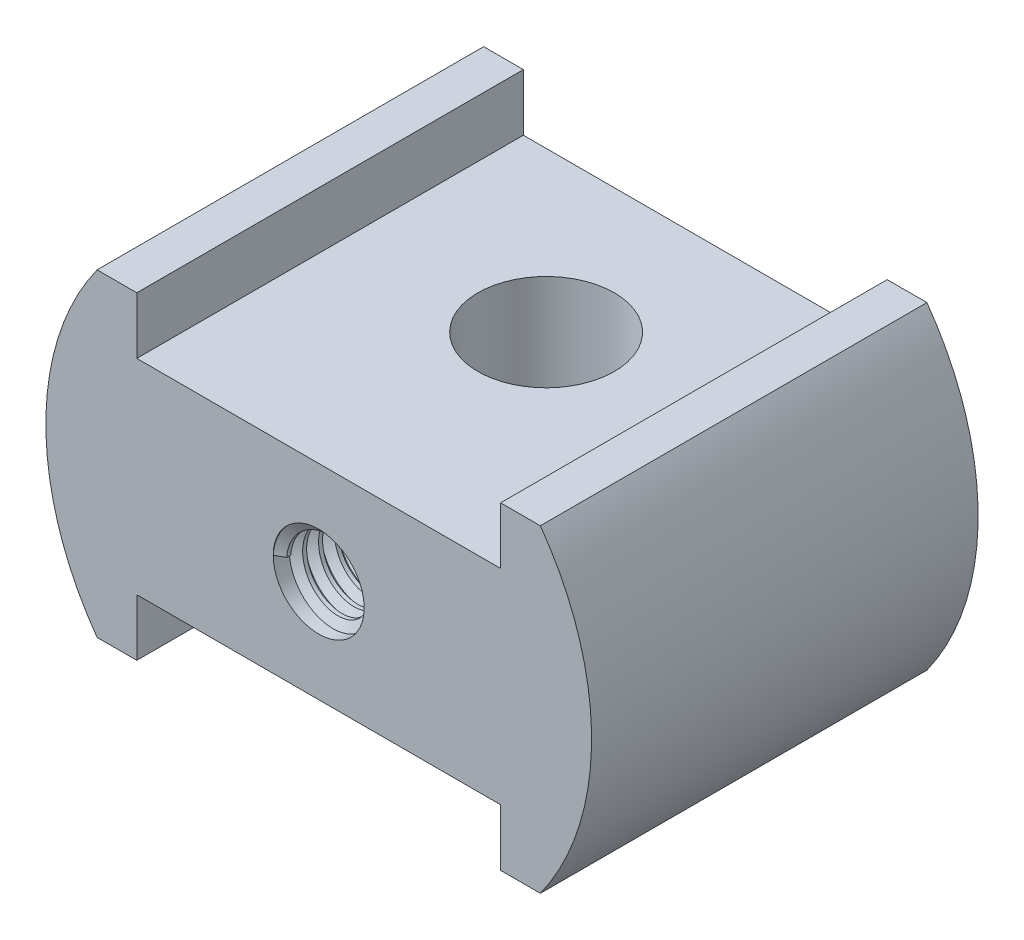
SolidWorks part; units mm, degrees
ref_plane "Front Plane" through (0, 0, 0) normal (0, 0, 1) x (1, 0, 0)
ref_plane "Top Plane" through (0, 0, 0) normal (0, 1, 0) x (1, 0, 0)
ref_plane "Right Plane" through (0, 0, 0) normal (1, 0, 0) x (0, 0, -1)
sketch "Sketch1" plane through (0, 0, 0) normal (0, 0, 1) x (1, 0, 0)
  line L5 (0, 0) -> (0, 2.5)
  line L6 (0, 2.5) -> (16, 2.5)
  line L14 (16, 2.5) -> (16, 0)
  line L15 (16, 0) -> (17.7468, 0)
  line L16 (0, 0) -> (-1.7468, 0)
  line L17 (-1.7468, 14) -> (0, 14)
  line L18 (0, 14) -> (0, 11.5)
  line L19 (0, 11.5) -> (16, 11.5)
  line L20 (16, 11.5) -> (16, 14)
  line L21 (16, 14) -> (17.7468, 14)
  arc A2 (-1.7468, 14) -> (-1.7468, 0) centre (8, 7) ccw
  arc A3 (17.7468, 14) -> (17.7468, 0) centre (8, 7) cw
  point P7 (20, 7)
  point P15 (18.0219, 14)
  point P16 (-4, 7)
  point P17 (-4.4057, 7)
  point P18 (3.1214, 7)
  point P19 (-4, 7)
  point P20 (-2.1015, 14)
  point P21 (-4, 7)
  point P22 (-1.6406, 14)
  dimension "D3" = 2.5
  dimension "D6" = 4.5
  dimension "D5" = 4
  dimension "D1" = 16
  dimension "D2" = 9
  dimension "D4" = 4
extrude "Boss-Extrude1" add sketch "Sketch1" along normal blind 17
sketch "Sketch2" plane through (0, 2.5, 0) normal (0, -1, 0) x (1, 0, 0)
  line L0 (0, 0) -> (16, 0) construction
  circle A0 centre (8, 7) radius 3
  dimension "D1" = 7
  dimension "D2" = 6
extrude "Cut-Extrude1" cut sketch "Sketch2" against normal through all
sketch "Sketch3" plane through (0, 0, 17) normal (0, 0, 1) x (1, 0, 0)
  circle A0 centre (8, 7) radius 2
  dimension "D1" = 4
extrude "Cut-Extrude2" cut sketch "Sketch3" against normal blind 6.5
thread "Thread1" pitch 0.7 method extrude profile "Thread Profile1" start angle 0, offset 0, length 6.5, pitch 0.7, diameter 4
ref_plane "Plane1" through (6, 7, 17) normal (0, -1, 0) x (-1, 0, 0)
sketch "Thread Profile1" plane through (6, 7, 17) normal (0, -1, 0) x (-1, 0, 0)
  line L0 (0, 0) -> (0, 0.7) construction
  line L11 (0, 0) -> (0, 0.6125)
  line L12 (0, 0.6125) -> (-0.3789, 0.3937)
  line L13 (-0.3789, 0.3937) -> (-0.3789, 0.2187)
  line L15 (-0.3789, 0.2187) -> (0, 0)
  line L17 (-0.3789, 0.3062) -> (0, 0.3062) construction
  point P2 (0, 0)
  dimension "Pitch" = 0.7
  dimension "Profile_Angle" = 60
  dimension "Profile_Land" = 0.175
  dimension "Profile_Height" = 0.3789
